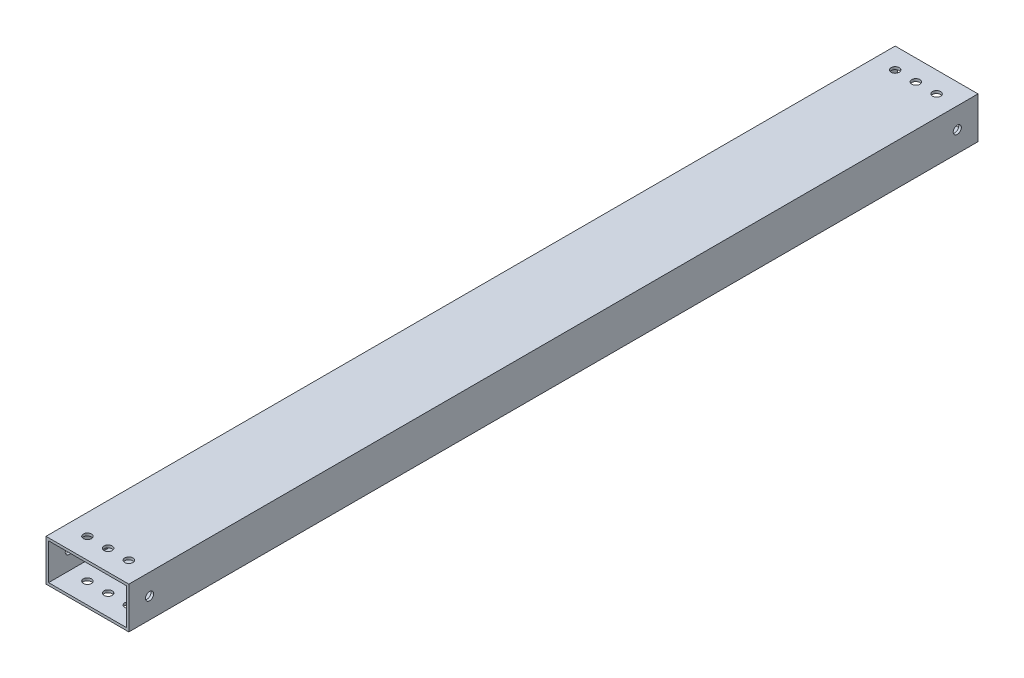
SolidWorks part; units mm, degrees
material "6061-T6 (SS)"
ref_plane "Front Plane" through (0, 0, 0) normal (0, 0, 1) x (1, 0, 0)
ref_plane "Top Plane" through (0, 0, 0) normal (0, 1, 0) x (1, 0, 0)
ref_plane "Right Plane" through (0, 0, 0) normal (1, 0, 0) x (0, 0, -1)
sketch "Sketch1" plane through (0, 0, 0) normal (0, 0, 1) x (1, 0, 0)
  line L0 (-23.8125, 11.1125) -> (23.8125, 11.1125)
  line L1 (-25.4, -12.7) -> (25.4, -12.7)
  line L2 (-25.4, -12.7) -> (-25.4, 12.7)
  line L3 (-25.4, 12.7) -> (25.4, 12.7)
  line L4 (25.4, -12.7) -> (25.4, 12.7)
  line L5 (-25.4, -12.7) -> (25.4, 12.7) construction
  line L6 (-25.4, 12.7) -> (25.4, -12.7) construction
  line L7 (23.8125, -11.1125) -> (23.8125, 11.1125)
  line L8 (-23.8125, -11.1125) -> (23.8125, -11.1125)
  line L9 (-23.8125, -11.1125) -> (-23.8125, 11.1125)
  point P0 (0, 0)
  dimension "D1" = 50.8
  dimension "D2" = 25.4
  dimension "D3" = 1.5875
extrude "Boss-Extrude1" add sketch "Sketch1" along normal mid plane 520.7
sketch "Sketch2" plane through (0, 12.7, 0) normal (0, 1, 0) x (1, 0, 0)
  line L0 (25.4, 260.35) -> (-25.4, 260.35) construction
  line L1 (-25.4, 0) -> (25.4, 0) construction
  line L2 (-25.4, -260.35) -> (-25.4, 260.35) construction
  line L3 (25.4, -260.35) -> (25.4, 260.35) construction
  circle A0 centre (-12.7, 247.65) radius 2.4892
  circle A1 centre (0, 247.65) radius 2.4892
  circle A2 centre (12.7, 247.65) radius 2.4892
  circle A3 centre (12.7, -247.65) radius 2.4892
  circle A4 centre (0, -247.65) radius 2.4892
  circle A5 centre (-12.7, -247.65) radius 2.4892
  point P9 (0, 260.35)
  dimension "D1" = 4.9784
  dimension "D2" = 12.7
  dimension "D3" = 12.7
  dimension "D4" = 12.7
extrude "Cut-Extrude1" cut sketch "Sketch2" against normal through all
sketch "Sketch3" plane through (25.4, 0, 0) normal (1, 0, 0) x (0, 0, -1)
  line L0 (260.35, -12.7) -> (260.35, 12.7) construction
  line L1 (0, 12.7) -> (0, -12.7) construction
  line L2 (-260.35, 12.7) -> (260.35, 12.7) construction
  line L3 (-260.35, -12.7) -> (260.35, -12.7) construction
  circle A0 centre (247.65, 0) radius 2.4892
  circle A1 centre (-247.65, 0) radius 2.4892
  point P5 (260.35, 0)
  dimension "D1" = 12.7
  dimension "D2" = 4.9784
extrude "Cut-Extrude2" cut sketch "Sketch3" against normal through all
